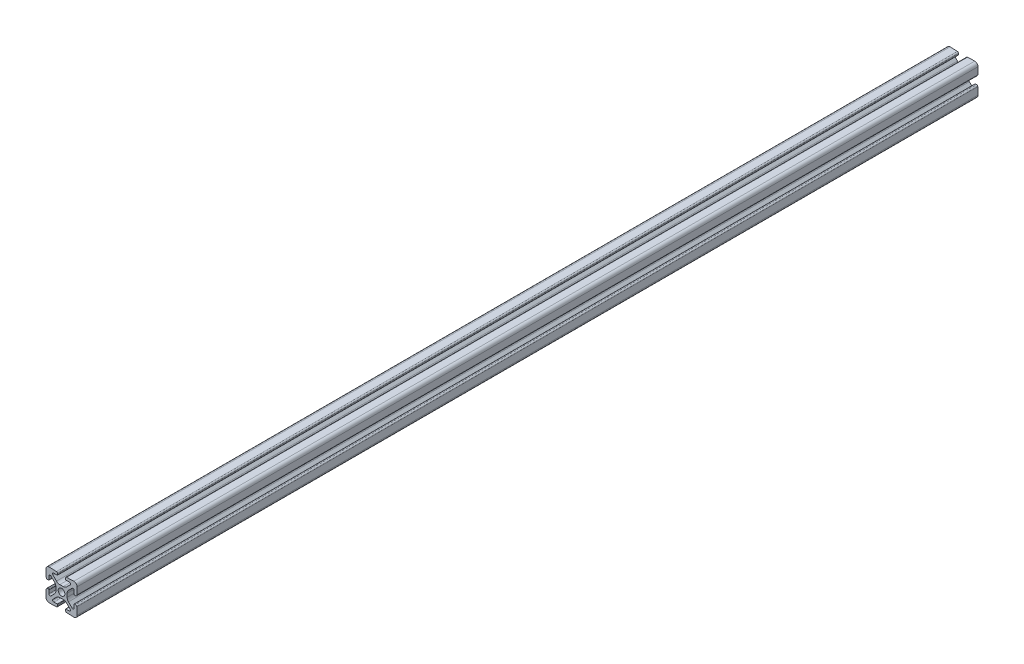
SolidWorks part; units mm, degrees
ref_plane "Front Plane" through (0, 0, 0) normal (0, 0, 1) x (1, 0, 0)
ref_plane "Top Plane" through (0, 0, 0) normal (0, 1, 0) x (1, 0, 0)
ref_plane "Right Plane" through (0, 0, 0) normal (1, 0, 0) x (0, 0, -1)
sketch "Sketch1" plane through (0, 0, 0) normal (0, 0, 1) x (1, 0, 0)
  line L0 (0, 0) -> (0, 10) construction
  line L1 (0, 0) -> (10, 0) construction
  line L2 (0, 0) -> (-10, 10) construction
  line L3 (-7.9302, 9.9988) -> (-3.2721, 9.8361)
  line L4 (-10, 10) -> (0, 10) construction
  line L6 (-2.8352, 8.0198) -> (-4.953, 8.0937)
  line L10 (0, 3.6) -> (-1.1022, 3.6)
  line L11 (-3.2236, 4.4787) -> (-5.5244, 6.7796)
  line L24 (0, 0) -> (-10, 0) construction
  line L25 (-10, 0) -> (0, 0) construction
  line L26 (0, 0) -> (0, -10) construction
  line L27 (-10, -10) -> (-10, 10) construction
  line L28 (0, 10) -> (10, 10) construction
  line L29 (-2.5249, 8.3091) -> (-2.5005, 9.0087)
  line L30 (-10, -10) -> (10, -10) construction
  arc A0 (-9.4142, 9.4142) -> (-7.9302, 9.9988) centre (-8, 8) cw
  arc A5 (-3.2721, 9.8361) -> (-2.5005, 9.0087) centre (-3.3, 9.0366) cw
  arc A6 (-1.1022, 3.6) -> (-3.2236, 4.4787) centre (-1.1022, 6.6) cw
  circle A16 centre (0, 0) radius 2.15
  arc A18 (-5.5244, 6.7796) -> (-4.953, 8.0937) centre (-4.9799, 7.3241) cw
  arc A20 (-2.8352, 8.0198) -> (-2.5249, 8.3091) centre (-2.8247, 8.3196) ccw
  point P15 (0, 0)
  point P42 (-2.3449, 3.6)
  point P80 (-10, 0)
  point P85 (0, -10)
  point P88 (0, -10)
  dimension "D11" = 2
  dimension "D15" = 3
  dimension "Center Hole Diameter" = 4.3
  dimension "D7" = 0.8
  dimension "D8" = 0.3
  dimension "D4" = 0.7701
  dimension "D1" = 45
  dimension "D2" = 2
  dimension "Rail Width" = 20
  dimension "T-Slot Depth" = 6.4
  dimension "D9" = 1.8
  dimension "Rail Height" = 20
  dimension "D23" = 7.2
  dimension "D5" = 11.5
  dimension "T-Slot Width" = 5
  dimension "D3" = 1.775
  dimension "D6" = 9.9598
sketch "Sketch2" plane through (0, 0, 0) normal (1, 0, 0) x (0, 0, -1)
  line L0 (-304.8, 0) -> (304.8, 0)
  line L1 (-304.8, -10) -> (-304.8, 10)
  line L2 (0, 0) -> (0, 10) construction
  line L3 (0, 0) -> (0, 10) construction
  line L4 (304.8, -10) -> (304.8, 10)
  point P0 (-274.8, 0)
  point P3 (0, 0)
  point P7 (274.8, 0)
  point P11 (-304.8, 0)
  point P14 (304.8, 0)
  dimension "D1" = 30
  dimension "Length" = 609.6
sketch "Sketch3" plane through (0, 0, 0) normal (0, 0, 1) x (1, 0, 0)
  line L0 (-2.5249, 8.3091) -> (-2.5005, 9.0087) construction
  line L1 (0, 0) -> (-10, 10) construction
  line L2 (0, 0) -> (-10, 10) construction
  line L5 (-7.9302, 9.9988) -> (-3.2721, 9.8361) construction
  line L6 (-2.8352, 8.0198) -> (-4.953, 8.0937) construction
  line L17 (-2.5249, 8.3091) -> (-2.5005, 9.0087)
  line L19 (-2.8352, 8.0198) -> (-4.953, 8.0937)
  line L20 (0, 0) -> (0, 10) construction
  line L21 (-3.6, 0) -> (-2.15, 0)
  line L22 (-3.6, 0) -> (-3.6, 1.1022)
  line L23 (-4.4787, 3.2236) -> (-6.7796, 5.5244)
  line L42 (-3.2236, 4.4787) -> (-5.5244, 6.7796) construction
  line L43 (0, 3.6) -> (-1.1022, 3.6) construction
  line L44 (-7.9302, 9.9988) -> (-3.2721, 9.8361)
  line L47 (-3.2236, 4.4787) -> (-5.5244, 6.7796)
  line L48 (0, 3.6) -> (-1.1022, 3.6)
  line L59 (0, 3.6) -> (0, 2.15)
  line L60 (-9.9988, 7.9302) -> (-9.8361, 3.2721)
  line L61 (-8.0198, 2.8352) -> (-8.0937, 4.953)
  line L62 (-8.3091, 2.5249) -> (-9.0087, 2.5005)
  arc A0 (-7.9302, 9.9988) -> (-9.4142, 9.4142) centre (-8, 8) ccw construction
  arc A1 (-2.8352, 8.0198) -> (-2.5249, 8.3091) centre (-2.8247, 8.3196) ccw construction
  arc A3 (-2.8352, 8.0198) -> (-2.5249, 8.3091) centre (-2.8247, 8.3196) ccw
  arc A5 (-7.9302, 9.9988) -> (-9.9988, 7.9302) centre (-8, 8) ccw
  circle A13 centre (0, 0) radius 2.15 construction
  arc A14 (0, 2.15) -> (-2.15, 0) centre (0, 0) ccw
  arc A15 (-4.4787, 3.2236) -> (-3.6, 1.1022) centre (-6.6, 1.1022) cw
  arc A16 (-8.0937, 4.953) -> (-6.7796, 5.5244) centre (-7.3241, 4.9799) cw
  arc A17 (-9.0087, 2.5005) -> (-9.8361, 3.2721) centre (-9.0366, 3.3) cw
  arc A18 (-8.0198, 2.8352) -> (-8.3091, 2.5249) centre (-8.3196, 2.8247) cw
  arc A36 (-2.5005, 9.0087) -> (-3.2721, 9.8361) centre (-3.3, 9.0366) ccw construction
  arc A38 (-4.953, 8.0937) -> (-5.5244, 6.7796) centre (-4.9799, 7.3241) ccw construction
  arc A39 (-3.2236, 4.4787) -> (-1.1022, 3.6) centre (-1.1022, 6.6) ccw construction
  arc A41 (-2.5005, 9.0087) -> (-3.2721, 9.8361) centre (-3.3, 9.0366) ccw
  arc A43 (-4.953, 8.0937) -> (-5.5244, 6.7796) centre (-4.9799, 7.3241) ccw
  arc A44 (-3.2236, 4.4787) -> (-1.1022, 3.6) centre (-1.1022, 6.6) ccw
extrude "Boss-Extrude1" add sketch "Sketch3" along normal mid plane 609.6
pattern_circular "CirPattern1" count 4 over 360 about axis through (0, 0, 304.8) along (0, 0, -1) of "Boss-Extrude1"
ref_plane "Contact Plane 1" through (0, 10, 0) normal (0, 1, 0) x (1, 0, 0)
ref_plane "Contact Plane 2" through (10, 0, 0) normal (1, 0, 0) x (0, 0, -1)
ref_plane "Contact Plane 3" through (0, -10, 0) normal (0, -1, 0) x (-1, 0, 0)
ref_plane "Contact Plane 4" through (-10, 0, 0) normal (-1, 0, 0) x (0, 0, 1)
sketch "Sketch4" plane through (0.3391, 9.71, 0) normal (0.0349, 0.9994, 0) x (0.9994, -0.0349, 0)
  line L0 (-10.3099, -275.2) -> (10.3067, -275.2)
  line L1 (10.3067, -275.2) -> (10.3067, -309.2762)
  line L2 (10.3067, -309.2762) -> (-10.3099, -309.2762)
  line L3 (-10.3099, -309.2762) -> (-10.3099, -275.2)
extrude "Cut-Extrude1" cut sketch "Sketch4" against normal through all both and the other way through all
equation "\"D1@Sketch2\"=\"Rail Width@Sketch1\"*1.5"
equation "\"D1@Boss-Extrude1\" = \"Length@Sketch2\""
